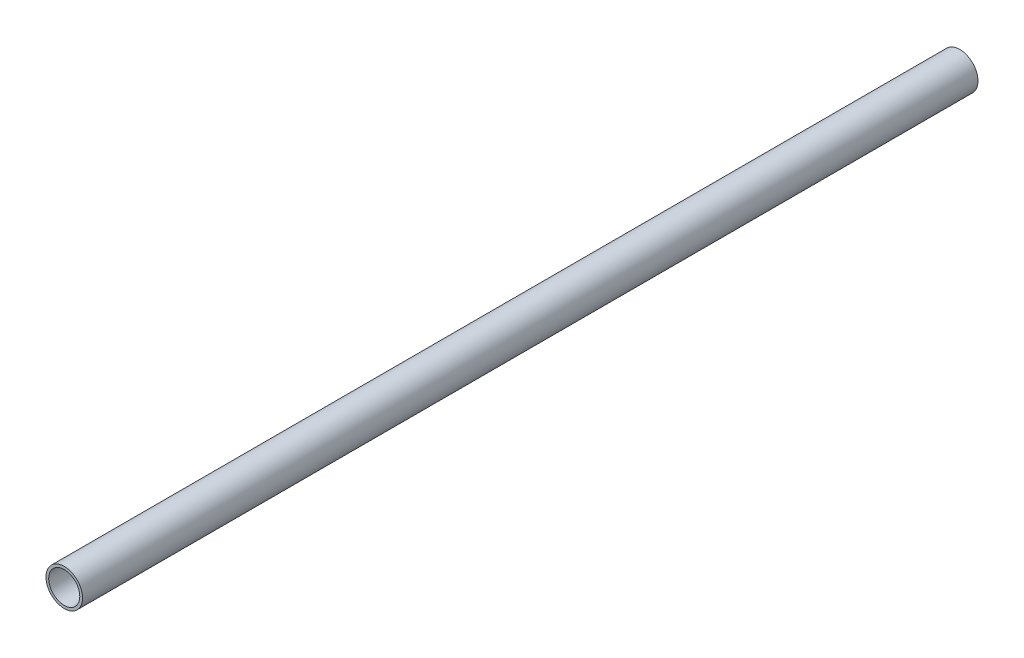
SolidWorks part; units mm, degrees
material "PE Высокой плотности"
ref_plane "Front" through (0, 0, 0) normal (0, 0, 1) x (1, 0, 0)
ref_plane "Top" through (0, 0, 0) normal (0, 1, 0) x (1, 0, 0)
ref_plane "Side" through (0, 0, 0) normal (1, 0, 0) x (0, 0, -1)
sketch "PipeSketch" plane through (0, 0, 0) normal (0, 0, 1) x (1, 0, 0)
  circle A0 centre (0, 0) radius 10
  circle A1 centre (0, 0) radius 8.5
  dimension "OuterDiameter" = 20
  dimension "InnerDiameter" = 17
extrude "Extrusion" add sketch "PipeSketch" along normal blind 490
sketch "FilterSketch" plane through (0, 0, 0) normal (0, 0, 1) x (1, 0, 0)
  circle A0 centre (0, 0) radius 10 construction
  dimension "NominalDiameter" = 20
